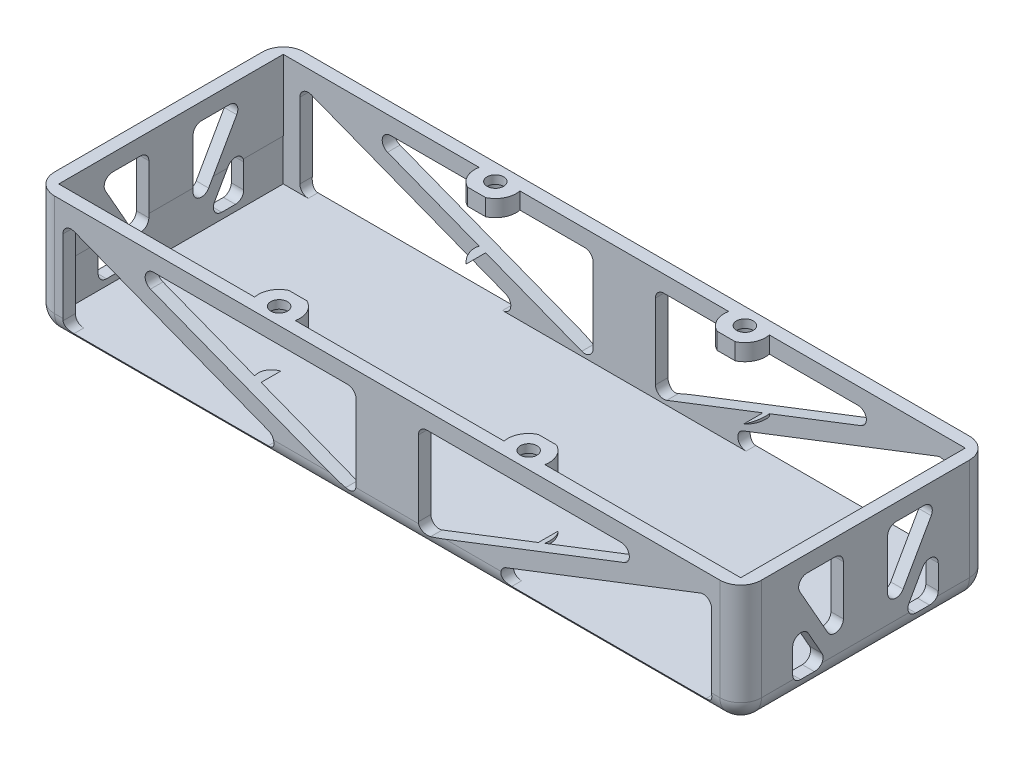
SolidWorks part; units mm, degrees
other "標示1"
sketch "草圖14" plane through (115, 29, -55) normal (0.5035, 0.4992, -0.7052) x (-0.8217, 0.0247, -0.5693)
material "ABS"
ref_plane "前基準面" through (0, 0, 0) normal (0, 0, 1) x (1, 0, 0)
ref_plane "上基準面" through (0, 0, 0) normal (0, 1, 0) x (1, 0, 0)
ref_plane "右基準面" through (0, 0, 0) normal (1, 0, 0) x (0, 0, -1)
other "質量中心"
sketch "草圖1" plane through (0, 0, 0) normal (0, 1, 0) x (1, 0, 0)
  line L2 (-85, -30) -> (-85, 30)
  line L4 (85, -30) -> (85, 30)
  line L5 (-85, -30) -> (85, 30) construction
  line L6 (-85, 30) -> (85, -30) construction
  line L9 (-1000, 0) -> (49000, 0) construction
  line L10 (0, -1000) -> (0, 0) construction
  line L20 (-85, 30) -> (85, 30)
  line L24 (0, 30) -> (0, 49000) construction
  line L25 (-85, -30) -> (85, -30)
  point P0 (0, 0)
  dimension "D1" = 170
  dimension "D2" = 60
extrude "填料-伸長1" add sketch "草圖1" along normal blind 2.5
sketch "草圖3" plane through (0, 2.5, 0) normal (0, 1, 0) x (1, 0, 0)
  line L0 (-980, 0) -> (-85, 0) construction
  line L1 (-85, -30) -> (-20, -30)
  line L2 (-85, -30) -> (-85, 0)
  line L7 (-20, -21.5) -> (-82, -21.5)
  line L8 (-82, 0) -> (-82, -21.5)
  line L9 (0, -1000) -> (0, 49000) construction
  line L10 (85, -30) -> (20, -30)
  line L12 (20, -21.5) -> (82, -21.5)
  line L13 (82, 0) -> (82, -21.5)
  line L15 (85, -30) -> (85, 0)
  line L16 (85, 30) -> (85, 0)
  line L18 (82, 0) -> (82, 21.5)
  line L19 (20, 21.5) -> (82, 21.5)
  line L21 (85, 30) -> (20, 30)
  line L22 (-85, 30) -> (-20, 30)
  line L24 (-20, 21.5) -> (-82, 21.5)
  line L25 (-82, 0) -> (-82, 21.5)
  line L27 (-85, 30) -> (-85, 0)
  line L29 (-20, -30) -> (20, -30)
  line L31 (-20, -21.5) -> (20, -21.5)
  line L35 (-20, 30) -> (20, 30)
  line L36 (-20, 21.5) -> (20, 21.5)
  line L37 (-82, 0) -> (82, 0) construction
  line L38 (85, 0) -> (49020, 0) construction
  line L39 (-85, 30) -> (-85, -30) construction
  dimension "D1" = 30
  dimension "D3" = 8.5
  dimension "D4" = 40
  dimension "D5" = 3
extrude "填料-伸長3" add sketch "草圖3" along normal blind 27
sketch "草圖6" plane through (0, 0, -21.5) normal (0, 0, 1) x (1, 0, 0)
  line L0 (0, -1000) -> (0, 49000) construction
  line L1 (82, 2.5) -> (-82, 2.5) construction
  line L2 (-1000, 14) -> (49000, 14) construction
  line L3 (82, 29.5) -> (-82, 29.5) construction
  line L31 (-82, 29.5) -> (-82, 2.5) construction
  line L35 (-66.9191, 25.5) -> (-7.5, 25.5)
  line L36 (-78, 25.5) -> (-78, 2.5)
  line L37 (-78, 2.5) -> (-18.5809, 2.5)
  line L38 (-7.5, 25.5) -> (-7.5, 2.5)
  line L40 (7.5, 25.5) -> (7.5, 2.5)
  line L41 (78, 2.5) -> (18.5809, 2.5)
  line L42 (78, 25.5) -> (78, 2.5)
  line L43 (66.9191, 25.5) -> (7.5, 25.5)
  line L56 (-78, 25.5) -> (-18.5809, 2.5)
  line L58 (-7.5, 2.5) -> (-66.9191, 25.5)
  line L61 (7.5, 2.5) -> (66.9191, 25.5)
  line L62 (78, 25.5) -> (18.5809, 2.5)
  dimension "D1" = 4
  dimension "D2" = 15
  dimension "D3" = 4
  dimension "D4" = 4
extrude "除料-伸長3" cut sketch "草圖6" against normal through all both and the other way through all
sketch "草圖7" plane through (82, 0, 0) normal (-1, 0, 0) x (0, 0, 1)
  line L0 (0, -1000) -> (0, 49000) construction
  line L1 (-1000, 14.75) -> (49000, 14.75) construction
  line L2 (17.5, 25.5) -> (5.3219, 4)
  line L3 (5.3219, 4) -> (5.3219, 25.5)
  line L4 (5.3219, 25.5) -> (17.5, 25.5)
  line L11 (-5.3219, 4) -> (-5.3219, 25.5)
  line L12 (17.5, 4) -> (8.7697, 4)
  line L13 (17.5, 19.413) -> (17.5, 4)
  line L14 (8.7697, 4) -> (17.5, 19.413)
  line L21 (-17.5, 19.413) -> (-17.5, 4)
  line L22 (-8.7697, 4) -> (-17.5, 19.413)
  line L23 (-17.5, 4) -> (-8.7697, 4)
  line L30 (-30, 29.5) -> (30, 29.5) construction
  line L31 (-30, 0) -> (30, 0) construction
  line L32 (-17.5, 25.5) -> (-5.3219, 4)
  line L33 (-5.3219, 25.5) -> (-17.5, 25.5)
  line L34 (-21.5, 29.5) -> (-21.5, 2.5) construction
  dimension "D1" = 3
  dimension "D2" = 4
  dimension "D3" = 4
  dimension "D4" = 4
extrude "除料-伸長4" cut sketch "草圖7" against normal through all both and the other way through all
fillet "圓角2" radius 2 48 edges at (83.5, 4, -17.5) (83.5, 4, 8.7697) (83.5, 4, 17.5) (83.5, 4, -8.7697) (83.5, 19.413, -17.5) (83.5, 19.413, 17.5) (-83.5, 4, 8.7697) (-83.5, 19.413, 17.5) (-83.5, 4, 17.5) (-83.5, 4, -17.5) (-83.5, 19.413, -17.5) (-83.5, 4, -8.7697) (7.5, 2.5, -25.75) (78, 25.5, -25.75) (66.9191, 25.5, -25.75) (-66.9191, 25.5, -25.75) (-78, 25.5, -25.75) (-7.5, 2.5, -25.75) (-78, 25.5, 25.75) (-66.9191, 25.5, 25.75) (-7.5, 2.5, 25.75) (66.9191, 25.5, 25.75) (7.5, 2.5, 25.75) (83.5, 25.5, 17.5) (83.5, 25.5, -5.3219) (83.5, 25.5, -17.5) (83.5, 25.5, 5.3219) (83.5, 4, 5.3219) (83.5, 4, -5.3219) (-83.5, 25.5, 17.5) (-83.5, 25.5, 5.3219) (-83.5, 4, 5.3219) (-83.5, 4, -5.3219) (-83.5, 25.5, -17.5) (-83.5, 25.5, -5.3219) (7.5, 25.5, -25.75) (-7.5, 25.5, -25.75) (7.5, 25.5, 25.75) (-7.5, 25.5, 25.75) (78, 25.5, 25.75) (78, 2.5, -25.75) (18.5809, 2.5, -25.75) (-78, 2.5, -25.75) (-18.5809, 2.5, -25.75) (-18.5809, 2.5, 25.75) (-78, 2.5, 25.75) (78, 2.5, 25.75) (18.5809, 2.5, 25.75)
sketch "草圖15" plane through (0, 25.5, 0) normal (0, -1, 0) x (1, 0, 0)
  line L0 (0, 0) -> (22.2822, 0) construction
  line L1 (0, 0) -> (0, 34.2486) construction
  line L2 (-85, 30) -> (85, 30) construction
  circle A0 centre (30, 26) radius 2
  circle A1 centre (-30, 26) radius 2
  circle A2 centre (30, -26) radius 2
  circle A3 centre (-30, -26) radius 2
  dimension "D2" = 4
  dimension "D1" = 4
  dimension "D3" = 30
extrude "除料-伸長5" cut sketch "草圖15" against normal through all
fillet "圓角3" radius 5 8 edges at (-85, 0, 0) (85, 0, 0) (0, 0, 30) (0, 0, -30) (-85, 14.75, 30) (85, 14.75, 30) (85, 14.75, -30) (-85, 14.75, -30)
sketch "草圖16" plane through (0, 29.5, 0) normal (0, 1, 0) x (1, 0, 0)
  line L0 (-82, 21.5) -> (-82, -21.5) construction
  line L1 (80, 30) -> (-80, 30) construction
  line L16 (0, 0) -> (0, 44.6367) construction
  line L17 (0, 0) -> (33.9902, 0) construction
  line L18 (-34.899, 27) -> (-82, 27)
  line L19 (25.101, 27) -> (-25.101, 27)
  line L24 (82, 27) -> (34.899, 27)
  line L25 (82, -27) -> (82, 27)
  line L26 (-82, -27) -> (-34.899, -27)
  line L27 (-82, 27) -> (-82, -27)
  line L28 (34.899, -27) -> (82, -27)
  line L29 (-25.101, -27) -> (25.101, -27)
  arc A20 (-34.899, 27) -> (-25.101, 27) centre (-30, 26) ccw
  arc A21 (34.899, 27) -> (25.101, 27) centre (30, 26) cw
  arc A22 (34.899, -27) -> (25.101, -27) centre (30, -26) ccw
  arc A23 (-34.899, -27) -> (-25.101, -27) centre (-30, -26) cw
  dimension "D2" = 10
  dimension "D1" = 3
extrude "除料-伸長6" cut sketch "草圖16" against normal up to surface (27 mm away) up to face at (0, 2.5, 0)
sketch "草圖17" plane through (0, 25.5, 0) normal (0, -1, 0) x (1, 0, 0)
  line L0 (0, 0) -> (0, 55.0894) construction
  line L1 (0, 0) -> (69.0254, 0) construction
  circle A0 centre (-30, 26) radius 3.55
  circle A1 centre (30, 26) radius 3.55
  circle A2 centre (30, -26) radius 3.55
  circle A3 centre (-30, -26) radius 3.55
  dimension "D1" = 7.1
extrude "除料-伸長7" cut sketch "草圖17" against normal blind 2
sketch "草圖18" plane through (0, 2.5, 0) normal (0, 1, 0) x (1, 0, 0)
  line L1 (-82.0088, -27) -> (82.0088, -27)
  line L2 (-82.0088, -27) -> (-82.0088, 27)
  line L3 (-82.0088, 27) -> (82.0088, 27)
  line L4 (82.0088, -27) -> (82.0088, 27)
  line L5 (-82.0088, -27) -> (82.0088, 27) construction
  line L6 (-82.0088, 27) -> (82.0088, -27) construction
  line L7 (80, 30) -> (-80, 30) construction
  point P0 (0, 0)
  dimension "D1" = 3
extrude "除料-伸長8" cut sketch "草圖18" along normal blind 10
